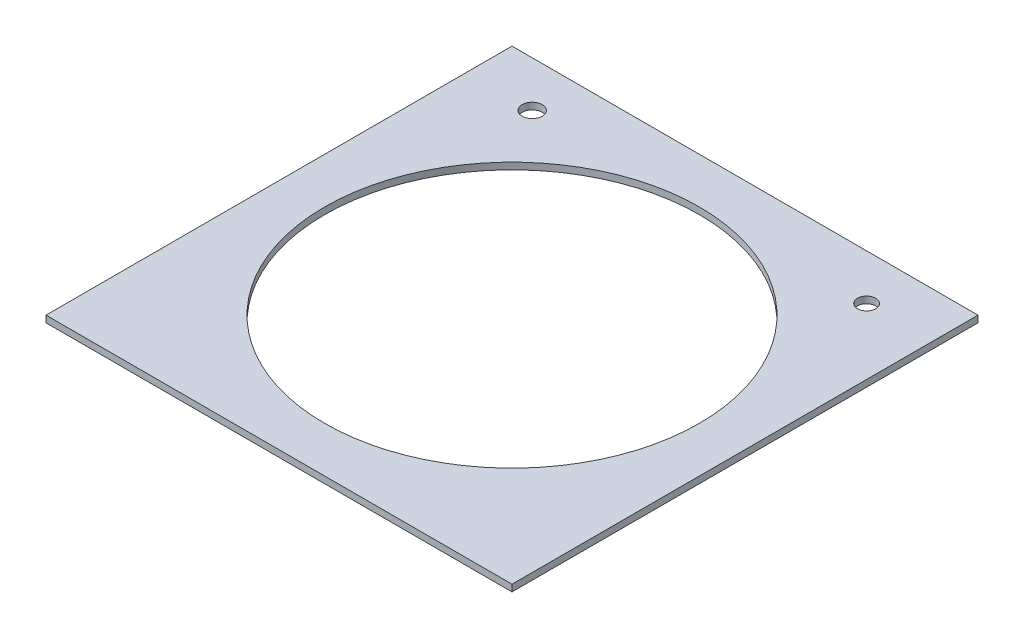
SolidWorks part; units mm, degrees
ref_plane "Front Plane" through (0, 0, 0) normal (0, 0, 1) x (1, 0, 0)
ref_plane "Top Plane" through (0, 0, 0) normal (0, 1, 0) x (1, 0, 0)
ref_plane "Right Plane" through (0, 0, 0) normal (1, 0, 0) x (0, 0, -1)
sketch "Sketch1" plane through (0, 0, 0) normal (0, 1, 0) x (1, 0, 0)
  line L1 (-34.8346, -34.8346) -> (34.8346, -34.8346)
  line L2 (-34.8346, -34.8346) -> (-34.8346, 34.8346)
  line L3 (-34.8346, 34.8346) -> (34.8346, 34.8346)
  line L4 (34.8346, -34.8346) -> (34.8346, 34.8346)
  circle A0 centre (-25, 28.0164) radius 1.5
  circle A1 centre (25, 28.0164) radius 1.3636
  circle A2 centre (0, 0) radius 28.0164
  point P0 (0, 0)
  point P5 (0, 0)
  point P16 (0, 28.0164)
extrude "Boss-Extrude1" add sketch "Sketch1" along normal blind 1
